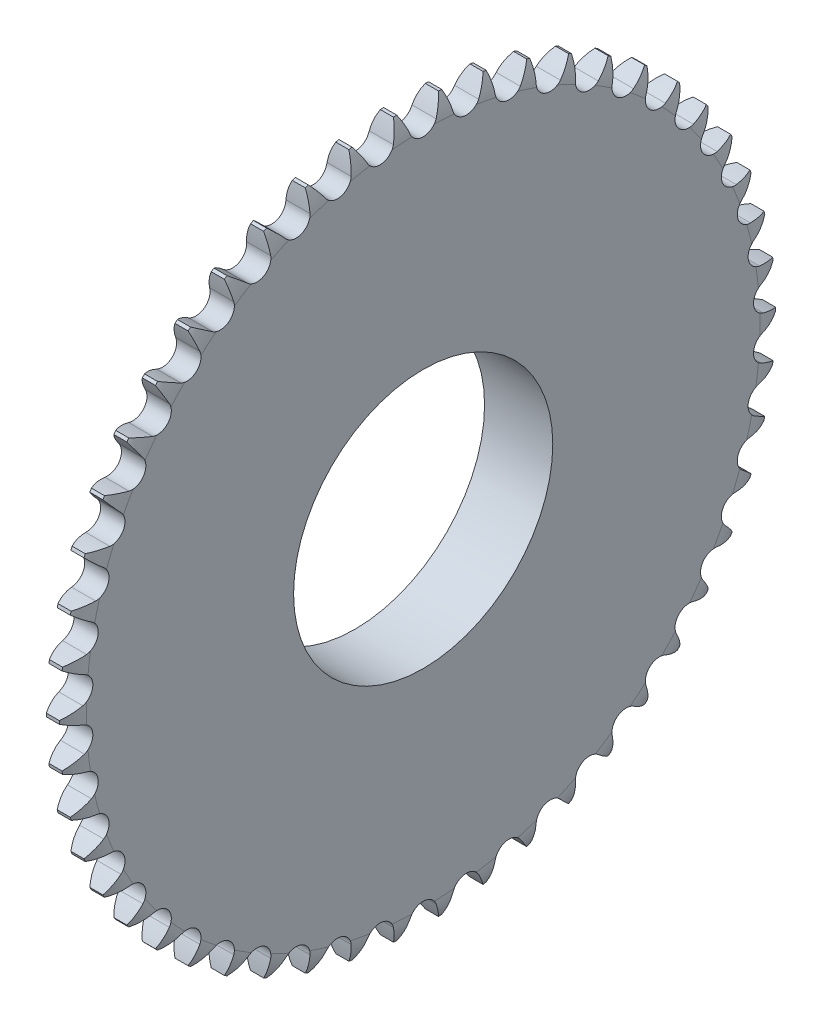
SolidWorks part; units mm, degrees
ref_plane "Plane1" through (0, 0, 0) normal (0, 0, 1) x (1, 0, 0)
ref_plane "Plane2" through (0, 0, 0) normal (0, 1, 0) x (1, 0, 0)
ref_plane "Plane3" through (0, 0, 0) normal (1, 0, 0) x (0, 0, -1)
sketch "Clipboard" plane through (0, 0, 0) normal (0, 1, 0) x (1, 0, 0)
  line L0 (0, 0) -> (10.2043, -12.161)
  line L1 (-15, 0) -> (100, 0) construction
  line L2 (0, 0) -> (-1.3675, 1.5456)
  line L3 (0, 0) -> (-14.8288, 5.6677)
  line L4 (0, 0) -> (1.9926, 2.3747)
  line L5 (0, 0) -> (-23.4238, -8.7364)
  line L6 (0, 0) -> (-7.4026, -4.9946)
  line L7 (-1.3675, 1.5456) -> (14.3658, 20.9747)
  line L8 (-76.2, 38.1) -> (-69.8, 38.1)
  line L9 (-73.5462, 42.5082) -> (-72.9534, 42.6013)
  line L10 (-74, 16.6356) -> (-55.89, 16.6356)
  circle A0 centre (0, 0) radius 5.08
  circle A1 centre (0, 0) radius 60
  circle A2 centre (0, 0) radius 60
  dimension "Num_teeth" = 50
  dimension "Thickness" = 8.93
sketch "BasProSke" plane through (0, 0, 0) normal (0, 1, 0) x (1, 0, 0)
  line L0 (-10, 0) -> (60, 0) construction
  line L1 (0, 0) -> (0, 123.4271)
  line L2 (0, 0) -> (8.93, 0)
  line L3 (8.93, 0) -> (8.93, 123.4271)
  line L4 (6.8662, 131.2543) -> (2.0637, 131.2543)
  arc A0 (0, 123.4271) -> (2.0637, 131.2543) centre (15.875, 123.4271) cw
  arc A1 (8.93, 123.4271) -> (6.8662, 131.2543) centre (-6.945, 123.4271) ccw
  dimension "D1" = 15.875
  dimension "Thickness" = 8.93
  dimension "Diameter" = 262.5085
revolve "Base-Revolve" add sketch "BasProSke" angle 360 about L0
sketch "TooCutSke" plane through (0, 0, 0) normal (1, 0, 0) x (0, 0, -1)
  line L0 (0, 126.4632) -> (4.7932, 124.6328) construction
  line L1 (0, 0) -> (0, 107) construction
  line L2 (0, 126.4632) -> (-10, 126.4632) construction
  line L3 (0, 126.4632) -> (-4.7932, 124.6328) construction
  arc A0 (4.7932, 124.6328) -> (7.9038, 131.517) centre (64.0203, 102.0162) cw
  arc A1 (4.7932, 124.6328) -> (-4.7932, 124.6328) centre (0, 126.4632) cw
  arc A2 (-4.7932, 124.6328) -> (-7.9038, 131.517) centre (-64.0203, 102.0162) ccw
  arc A3 (7.9038, 131.517) -> (-7.9038, 131.517) centre (0, 0) ccw
extrude "ToothCut" cut sketch "TooCutSke" along normal through all
pattern_circular "TeethCuts" count 50 every 7.2 about axis through (-10, 0, 0) along (1, 0, 0) of "ToothCut"
sketch "HubNeaOneSke" plane through (0, 0, 0) normal (-1, 0, 0) x (0, 0, 1)
  circle A0 centre (0, 0) radius 60
  dimension "Diameter" = 120
extrude "HubNearOne" add sketch "HubNeaOneSke" along normal blind 16.0705
fillet "HubNearOneFillet" radius 0.6 1 edges at (0, 0, -60)
sketch "HubNeaBotSke" plane through (0, 0, 0) normal (-1, 0, 0) x (0, 0, 1)
  circle A0 centre (0, 0) radius 60
  dimension "Diameter" = 120
extrude "HubNearBoth" [suppressed] add sketch "HubNeaBotSke" along normal blind 8.0352
fillet "HubNearBothFillet" [suppressed] radius 0.6
ref_plane "FarPln" through (8.93, 0, 0) normal (1, 0, 0) x (0, 0, -1)
sketch "HubFarSke" plane through (8.93, 0, 0) normal (1, 0, 0) x (0, 0, -1)
  circle A0 centre (0, 0) radius 60
  dimension "Diameter" = 120
extrude "HubFar" [suppressed] add sketch "HubFarSke" along normal blind 8.0352
fillet "HubFarFillet" [suppressed] radius 0.6
sketch "BorSke" plane through (0, 0, 0) normal (1, 0, 0) x (0, 0, -1)
  circle A0 centre (0, 0) radius 47.5
  dimension "Diameter" = 95
extrude "Bore" cut sketch "BorSke" along normal mid plane 50.001
sketch "KeySke" plane through (0, 0, 0) normal (1, 0, 0) x (0, 0, -1)
  line L0 (-14, 0) -> (-14, 53.9)
  line L1 (-14, 53.9) -> (14, 53.9)
  line L2 (14, 53.9) -> (14, 0)
  line L3 (0, 0) -> (0, 34) construction
  line L4 (-14, 0) -> (14, 0)
  dimension "Width" = 28
extrude "Keyway" [suppressed] cut sketch "KeySke" along normal mid plane 50.001
pattern_circular "Keyway2" [suppressed] count 2 every 90 about axis through (-10, 0, 0) along (1, 0, 0) reverse direction yes
equation "' \"Pitch@Clipboard\" = 12.7"
equation "' \"Num_strands@Clipboard\" = 1"
equation "' \"Num_teeth@Clipboard\" = 9"
equation "' \"Hub_dia@Clipboard\" = 50"
equation "' \"Overall_len@Clipboard\" = 3"
equation "' \"Diameter@BorSke\" = 12"
equation "' \"T_dim@Clipboard\" = 1"
equation "' \"Width@KeySke\" = 2"
equation "' \"Dr@Clipboard\" = 8.51"
equation "' \"Face_width@Clipboard\" = 7.2"
equation "' \"Side_radius@Clipboard\" = 12.7"
equation "' \"Side_relief@Clipboard\" = 1.27"
equation "' \"Transv_pitch@Clipboard\" = 13.92"
equation "' \"Show_teeth@Clipboard\" = 9"
equation "' \"Fillet_rad@Clipboard\" = 0.6"
equation "' \"Plate_wid@Clipboard\" = 11.8"
equation "\"Num_teeth@Clipboard\" = int( \"Num_teeth@Clipboard\" )"
equation "\"Num_teeth@Clipboard\" = ((sgn( \"Num_teeth@Clipboard\" - 5.0)+1)*( \"Num_teeth@Clipboard\" - 5.0))/2 +5.0"
equation "\"Num_teeth@Clipboard\" = ((sgn( \"Num_teeth@Clipboard\" - 200.0)-1)*( \"Num_teeth@Clipboard\" - 200.0))/-2 +200.0"
equation "\"MHD@Clipboard\" = \"Pitch@Clipboard\" * (1.0 / tan(3.14159265 / \"Num_teeth@Clipboard\" )) - 1.04 * \"Plate_wid@Clipboard\" - 0.76"
equation "\"Thickness@Clipboard\"  = \"Face_width@Clipboard\" + (\"Num_strands@Clipboard\" - 1) * \"Transv_pitch@Clipboard\""
equation "\"OAL@Clipboard\" = \"Thickness@Clipboard\" + 2 * \"Fillet_rad@Clipboard\" + 1"
equation "\"MHD@Clipboard\" = ((sgn( \"MHD@Clipboard\" - \"Hub_dia@Clipboard\" )-1)*( \"MHD@Clipboard\" - \"Hub_dia@Clipboard\" ))/-2+ \"Hub_dia@Clipboard\""
equation "\"OAL@Clipboard\" = ((sgn( \"OAL@Clipboard\" - \"Overall_len@Clipboard\" )+1)*( \"OAL@Clipboard\" - \"Overall_len@Clipboard\" ))/2 + \"Overall_len@Clipboard\" + 0.0005"
equation "\"Num_teeth@TeethCuts\" = int( \"Show_teeth@Clipboard\" ) + 1"
equation "\"Num_teeth@TeethCuts\" = ((sgn( \"Num_teeth@TeethCuts\" - \"Num_teeth@Clipboard\" )-1)*( \"Num_teeth@TeethCuts\" - \"Num_teeth@Clipboard\" ))/-2+ \"Num_teeth@Clipboard\""
equation "\"Num_teeth@TeethCuts\" = ((sgn( \"Num_teeth@TeethCuts\" - 2.0)+1)*( \"Num_teeth@TeethCuts\" - 2.0))/2 +2.0"
equation "\"Angle@TeethCuts\" = 360.0 / \"Num_teeth@Clipboard\""
equation "\"Seat_radius@TooCutSke\" = ( \"Pitch@Clipboard\" / 2.0) / sin(3.14159265 / \"Num_teeth@Clipboard\" ) - \"Dr@Clipboard\" / 2.0 + \"Dr@Clipboard\" * 0.505"
equation "\"R1@TooCutSke\"  = \"Dr@Clipboard\" * 0.505"
equation "\"X@TooCutSke\" = 140.0 - (90.0 / \"Num_teeth@Clipboard\")"
equation "\"R2@TooCutSke\" = 0.12 * \"Dr@Clipboard\" * ( \"Num_teeth@Clipboard\" + 2.0)"
equation "\"Overcut@TooCutSke\" = 0.5 + 0.625 * \"Pitch@Clipboard\" - 0.5 * \"Dr@Clipboard\"  +  \"Pitch@Clipboard\" / 2.0 / sin(3.14159265 / \"Num_teeth@Clipboard\" )"
equation "\"Diameter@BasProSke\" = 2.0 * ( 0.625 * \"Pitch@Clipboard\" - 0.5 * \"Dr@Clipboard\"  +  \"Pitch@Clipboard\" / 2.0 / sin(3.14159265 / \"Num_teeth@Clipboard\" ))"
equation "\"Thickness@BasProSke\"  = \"Thickness@Clipboard\""
equation "\"G1@BasProSke\" =  \"Side_relief@Clipboard\""
equation "\"G2@BasProSke\" =  \"Side_relief@Clipboard\""
equation "\"D1@BasProSke\" =  \"Side_radius@Clipboard\""
equation "\"Diameter@HubNeaOneSke\" = \"MHD@Clipboard\""
equation "\"Length@HubNearOne\" = \"OAL@Clipboard\" - \"Thickness@BasProSke\""
equation "\"Diameter@HubNeaBotSke\" = \"MHD@Clipboard\""
equation "\"Length@HubNearBoth\" = ( \"OAL@Clipboard\" - \"Thickness@BasProSke\" ) / 2.0"
equation "\"D1@HubNearOneFillet\" = \"Fillet_rad@Clipboard\""
equation "\"D1@HubNearBothFillet\" = \"Fillet_rad@Clipboard\""
equation "\"Thickness@FarPln\" = \"Thickness@BasProSke\""
equation "\"Diameter@HubFarSke\" = \"MHD@Clipboard\""
equation "\"Length@HubFar\" = ( \"OAL@Clipboard\" - \"Thickness@BasProSke\" ) / 2.0"
equation "\"D1@HubFarFillet\" = \"Fillet_rad@Clipboard\""
equation "\"D1@Bore\" = \"OAL@Clipboard\" * 2.0"
equation "\"D1@Keyway\" = \"OAL@Clipboard\" * 2.0"
equation "\"Offset@KeySke\" = \"T_dim@Clipboard\" + \"Diameter@BorSke\" / 2.0"
